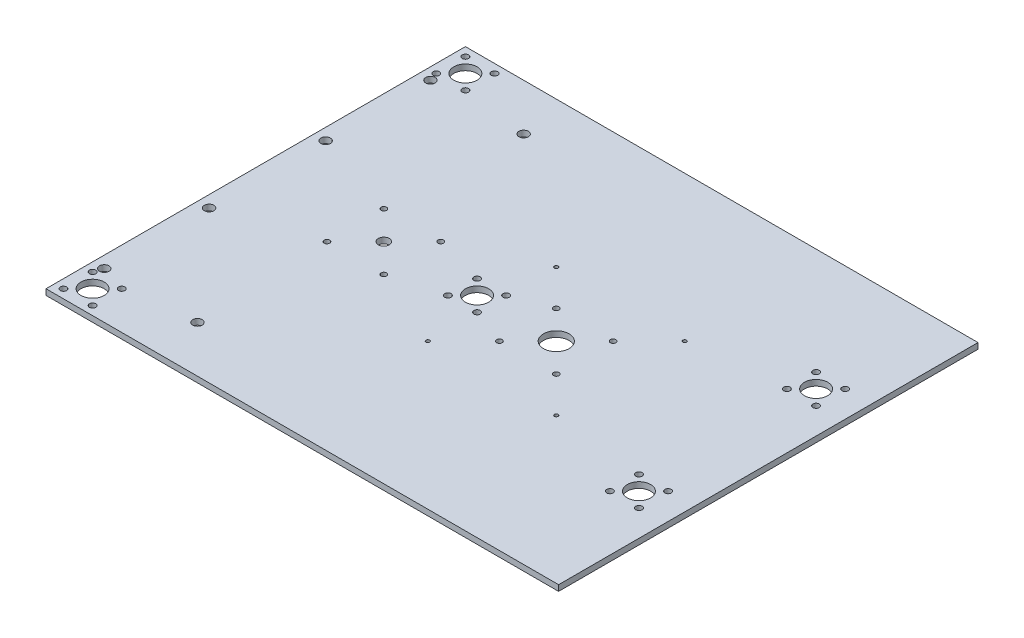
SolidWorks part; units mm, degrees
ref_plane "Front Plane" through (0, 0, 0) normal (0, 0, 1) x (1, 0, 0)
ref_plane "Top Plane" through (0, 0, 0) normal (0, 1, 0) x (1, 0, 0)
ref_plane "Right Plane" through (0, 0, 0) normal (1, 0, 0) x (0, 0, -1)
sketch "Sketch1" plane through (0, 0, 0) normal (0, 1, 0) x (1, 0, 0)
  line L1 (-139.7, -114.3) -> (139.7, -114.3)
  line L2 (-139.7, -114.3) -> (-139.7, 114.3)
  line L3 (-139.7, 114.3) -> (139.7, 114.3)
  line L4 (139.7, -114.3) -> (139.7, 114.3)
  line L5 (-139.7, -114.3) -> (139.7, 114.3) construction
  line L6 (-139.7, 114.3) -> (139.7, -114.3) construction
  point P0 (0, 0)
  dimension "D1" = 228.6
  dimension "D2" = 279.4
extrude "Boss-Extrude1" add sketch "Sketch1" along normal blind 3.175
sketch "Sketch2" plane through (0, 0, 0) normal (0, 1, 0) x (1, 0, 0)
  line L0 (-193.2668, 0) -> (192.9727, 0) construction
sketch "Sketch3" plane through (0, 3.175, 0) normal (0, 1, 0) x (1, 0, 0)
  circle A1 centre (-133.35, -31.75) radius 2.6
  circle A2 centre (-133.35, -31.75) radius 2.6
  circle A3 centre (-82.55, -88.9) radius 2.6
  circle A4 centre (-82.55, -88.9) radius 2.6
  circle A5 centre (-133.35, -88.9) radius 2.6
  circle A6 centre (-133.35, -88.9) radius 2.6
  dimension "D1" = 0
  dimension "D2" = 0
  dimension "D3" = 0
sketch "Sketch5" plane through (0, 3.175, 0) normal (0, 1, 0) x (1, 0, 0)
  circle A0 centre (-54.374, 15.5) radius 1.5 construction
  circle A1 centre (-54.374, -15.5) radius 1.5 construction
  circle A2 centre (-85.374, 15.5) radius 1.5 construction
  circle A3 centre (-85.374, -15.5) radius 1.5 construction
  circle A4 centre (-69.874, 0) radius 2.5 construction
  circle A5 centre (-54.374, 15.5) radius 1.5
  circle A6 centre (-54.374, -15.5) radius 1.5
  circle A7 centre (-85.374, 15.5) radius 1.5
  circle A8 centre (-85.374, -15.5) radius 1.5
  circle A9 centre (-69.874, 0) radius 2.5 construction
  circle A10 centre (-69.874, 0) radius 3.008
  dimension "D1" = 6.016
sketch "Sketch7" plane through (0, 3.175, 0) normal (0, 1, 0) x (1, 0, 0)
  circle A0 centre (59.1318, -35.0018) radius 1 construction
  circle A1 centre (-10.8718, -35.0018) radius 1 construction
  circle A2 centre (59.1318, -35.0018) radius 1
  circle A3 centre (-10.8718, -35.0018) radius 1
  circle A4 centre (-10.8718, 35.0018) radius 1 construction
  circle A5 centre (59.1318, 35.0018) radius 1 construction
  circle A6 centre (-10.8718, 35.0018) radius 1
  circle A7 centre (59.1318, 35.0018) radius 1
extrude "Cut-Extrude1" cut sketch "Sketch3" against normal through all
mirror "Mirror1" about plane through (0, 0, 0) normal (0, 0, 1) of "Cut-Extrude1"
extrude "Cut-Extrude2" cut sketch "Sketch5" against normal through all
extrude "Cut-Extrude3" cut sketch "Sketch7" against normal through all
sketch "Sketch9" plane through (0, 3.175, 0) normal (0, 1, 0) x (1, 0, 0)
  circle A0 centre (-119.0625, -109.5375) radius 1.727 construction
  circle A1 centre (-119.0625, -93.6625) radius 1.727 construction
  circle A2 centre (-134.9375, -93.6625) radius 1.727 construction
  circle A3 centre (-134.9375, -109.5375) radius 1.727 construction
  circle A4 centre (-127, -101.6) radius 6.35 construction
  circle A5 centre (-119.0625, -109.5375) radius 1.727
  circle A6 centre (-119.0625, -93.6625) radius 1.727
  circle A7 centre (-134.9375, -93.6625) radius 1.727
  circle A8 centre (-134.9375, -109.5375) radius 1.727
  circle A9 centre (-127, -101.6) radius 6.35
  circle A10 centre (125.4125, -56.1975) radius 1.727 construction
  circle A11 centre (125.4125, -40.3225) radius 1.727 construction
  circle A12 centre (117.475, -48.26) radius 6.35 construction
  circle A13 centre (109.5375, -40.3225) radius 1.727 construction
  circle A14 centre (109.5375, -56.1975) radius 1.727 construction
  circle A15 centre (125.4125, -56.1975) radius 1.727
  circle A16 centre (125.4125, -40.3225) radius 1.727
  circle A17 centre (117.475, -48.26) radius 6.35
  circle A18 centre (109.5375, -40.3225) radius 1.727
  circle A19 centre (109.5375, -56.1975) radius 1.727
  circle A20 centre (-11.1125, 7.9375) radius 1.727 construction
  circle A21 centre (-11.1125, -7.9375) radius 1.727 construction
  circle A22 centre (-19.05, 0) radius 6.35 construction
  circle A23 centre (-26.9875, -7.9375) radius 1.727 construction
  circle A24 centre (-26.9875, 7.9375) radius 1.727 construction
  circle A25 centre (-11.1125, 7.9375) radius 1.727
  circle A26 centre (-11.1125, -7.9375) radius 1.727
  circle A27 centre (-19.05, 0) radius 6.35
  circle A28 centre (-26.9875, -7.9375) radius 1.727
  circle A29 centre (-26.9875, 7.9375) radius 1.727
  circle A30 centre (109.5375, 56.1975) radius 1.727 construction
  circle A31 centre (109.5375, 40.3225) radius 1.727 construction
  circle A32 centre (125.4125, 56.1975) radius 1.727 construction
  circle A33 centre (117.475, 48.26) radius 6.35 construction
  circle A34 centre (125.4125, 40.3225) radius 1.727 construction
  circle A35 centre (109.5375, 56.1975) radius 1.727
  circle A36 centre (109.5375, 40.3225) radius 1.727
  circle A37 centre (125.4125, 56.1975) radius 1.727
  circle A38 centre (117.475, 48.26) radius 6.35
  circle A39 centre (125.4125, 40.3225) radius 1.727
  circle A40 centre (-119.0625, 93.6625) radius 1.727 construction
  circle A41 centre (-119.0625, 109.5375) radius 1.727 construction
  circle A42 centre (-134.9375, 109.5375) radius 1.727 construction
  circle A43 centre (-134.9375, 93.6625) radius 1.727 construction
  circle A44 centre (-119.0625, 93.6625) radius 1.727
  circle A45 centre (-119.0625, 109.5375) radius 1.727
  circle A46 centre (-134.9375, 109.5375) radius 1.727
  circle A47 centre (-134.9375, 93.6625) radius 1.727
  circle A48 centre (-127, 101.6) radius 6.35 construction
  circle A49 centre (-127, 101.6) radius 6.35
extrude "Cut-Extrude5" cut sketch "Sketch9" against normal through all both and the other way through all
sketch "Sketch11" plane through (0, 3.175, 0) normal (0, 1, 0) x (1, 0, 0)
  circle A0 centre (39.63, 15.5) radius 1.5 construction
  circle A1 centre (39.63, -15.5) radius 1.5 construction
  circle A2 centre (8.63, -15.5) radius 1.5 construction
  circle A3 centre (8.63, 15.5) radius 1.5 construction
  circle A4 centre (24.13, 0) radius 5.25 construction
  circle A5 centre (39.63, 15.5) radius 1.5
  circle A6 centre (39.63, -15.5) radius 1.5
  circle A7 centre (8.63, -15.5) radius 1.5
  circle A8 centre (8.63, 15.5) radius 1.5
  circle A9 centre (24.13, 0) radius 5.25 construction
  circle A10 centre (24.13, 0) radius 6.985
  dimension "D1" = 13.97
extrude "Cut-Extrude6" cut sketch "Sketch11" against normal through all both and the other way through all
equation "\"tightTol\"= 0.005in"
equation "\"normTol\"= 0.01in"
equation "\"looseTol\"= 0.02in"
equation "\"D1@Sketch5\"=5mm+2*\"looseTol\""
